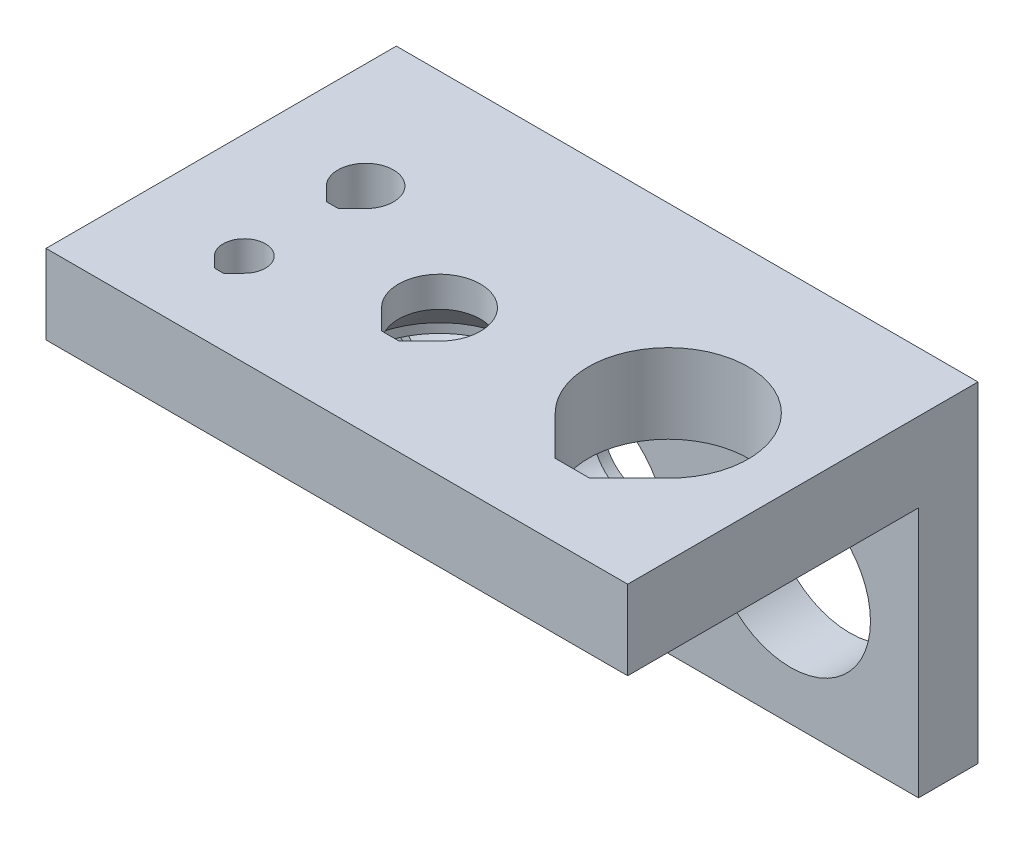
SolidWorks part; units mm, degrees
ref_plane "Front Plane" through (0, 0, 0) normal (0, 0, 1) x (1, 0, 0)
ref_plane "Top Plane" through (0, 0, 0) normal (0, 1, 0) x (1, 0, 0)
ref_plane "Right Plane" through (0, 0, 0) normal (1, 0, 0) x (0, 0, -1)
sketch "Sketch1" plane through (0, 0, 0) normal (0, 0, 1) x (1, 0, 0)
  line L1 (-22, -12.5) -> (22, -12.5)
  line L2 (-22, -12.5) -> (-22, 12.5)
  line L3 (-22, 12.5) -> (22, 12.5)
  line L4 (22, -12.5) -> (22, 12.5)
  line L5 (-22, -12.5) -> (22, 12.5) construction
  line L6 (-22, 12.5) -> (22, -12.5) construction
  point P0 (0, 0)
  dimension "D1" = 25
  dimension "D2" = 44
extrude "Boss-Extrude1" add sketch "Sketch1" along normal blind 4.5
sketch "Sketch2" plane through (0, 0, 4.5) normal (0, 0, 1) x (1, 0, 0)
  line L0 (22, -12.5) -> (22, 12.5) construction
  line L1 (-22, 12.5) -> (22, 12.5)
  line L2 (-22, 12.5) -> (-22, 6.5)
  line L3 (-22, 6.5) -> (22, 6.5)
  line L4 (22, 12.5) -> (22, 6.5)
  dimension "D1" = 6
extrude "Boss-Extrude2" add sketch "Sketch2" along normal blind 22
sketch "Sketch3" plane through (0, 0, 4.5) normal (0, 0, 1) x (1, 0, 0)
  line L0 (-22, -12.5) -> (22, -12.5) construction
  line L1 (-22, 6.5) -> (-22, -12.5) construction
  circle A0 centre (-14, -8.5) radius 1.6
  circle A1 centre (-14, 0.6825) radius 2.1
  circle A2 centre (-3.2346, -4.5) radius 3.1
  circle A3 centre (12.316, -2.7437) radius 6.05
  dimension "D1" = 3.2
  dimension "D2" = 4.2
  dimension "D3" = 6.2
  dimension "D4" = 12.1
  dimension "D5" = 4
  dimension "D6" = 8
  dimension "D7" = 8
extrude "Cut-Extrude1" cut sketch "Sketch3" against normal through all
sketch "Sketch4" plane through (0, 0, 4.5) normal (0, 0, 1) x (1, 0, 0)
  circle A0 centre (-3.2346, -4.5) radius 6.1
  dimension "D1" = 12.2
extrude "Cut-Extrude2" cut sketch "Sketch4" against normal blind 0.7
sketch "Sketch5" plane through (0, 0, 4.5) normal (0, 0, 1) x (1, 0, 0)
  circle A0 centre (-14, 0.6825) radius 4.1
  circle A1 centre (-14, 0.6825) radius 2.1 construction
  dimension "D1" = 8.2
extrude "Cut-Extrude3" cut sketch "Sketch5" against normal blind 0.5
sketch "Sketch6" plane through (0, 0, 4.5) normal (0, 0, 1) x (1, 0, 0)
  circle A0 centre (-14, -8.5) radius 3.1
  dimension "D1" = 6.2
extrude "Cut-Extrude4" cut sketch "Sketch6" against normal blind 0.4
chamfer "Chamfer4" distance 3 angle 45 1 edges at (-0.1346, -4.5, 3.8)
chamfer "Chamfer5" distance 2 angle 45 1 edges at (-11.9, 0.6825, 4)
chamfer "Chamfer6" distance 1.5 angle 45 1 edges at (-12.4, -8.5, 4.1)
ref_plane "Plane1" through (0, 5.5, 5.5) normal (0, -0.7071, -0.7071) x (1, 0, 0)
mirror "Mirror1" about plane through (0, 5.5, 5.5) normal (0, -0.7071, -0.7071) of "Chamfer6", "Chamfer5", "Chamfer4", "Cut-Extrude4", "Cut-Extrude3", "Cut-Extrude2", "Cut-Extrude1"
sketch "Sketch7" plane through (0, 12.5, 0) normal (0, 1, 0) x (1, 0, 0)
  line L0 (-14.3427, -21.42) -> (-13.6573, -21.42)
  line L1 (-13.6573, -21.42) -> (-12.8686, -20.6314)
  line L2 (-14.3427, -21.42) -> (-15.1314, -20.6314)
  line L3 (-14, -21.42) -> (-14, -19.5) construction
  line L4 (-15.1314, -20.6314) -> (-14, -19.5)
  line L5 (-14, -19.5) -> (-12.8686, -20.6314)
  line L6 (-3.2346, -15.5) -> (-1.0426, -17.692)
  line L7 (-1.0426, -17.692) -> (-2.5706, -19.22)
  line L8 (-3.8987, -19.22) -> (-5.4267, -17.692)
  line L9 (-5.4267, -17.692) -> (-3.2346, -15.5)
  line L10 (-3.8987, -19.22) -> (-2.5706, -19.22)
  line L11 (-3.2346, -15.5) -> (-3.2346, -19.22) construction
  line L12 (12.316, -13.7437) -> (16.594, -18.0216)
  line L13 (16.594, -18.0216) -> (13.622, -20.9937)
  line L14 (13.622, -20.9937) -> (11.01, -20.9937)
  line L15 (11.01, -20.9937) -> (8.038, -18.0216)
  line L16 (8.038, -18.0216) -> (12.316, -13.7437)
  line L17 (12.316, -20.9937) -> (12.316, -13.7437) construction
  line L18 (-14, -10.3175) -> (-12.5151, -11.8024)
  line L19 (-12.5151, -11.8024) -> (-13.5502, -12.8375)
  line L20 (-13.5502, -12.8375) -> (-14.4498, -12.8375)
  line L21 (-14.4498, -12.8375) -> (-15.4849, -11.8024)
  line L22 (-15.4849, -11.8024) -> (-14, -10.3175)
  line L23 (-14, -12.8375) -> (-14, -10.3175) construction
  circle A0 centre (-14, -19.5) radius 1.6 construction
  circle A1 centre (-3.2346, -15.5) radius 3.1 construction
  circle A2 centre (12.316, -13.7437) radius 6.05 construction
  circle A3 centre (-14, -10.3175) radius 2.1 construction
  point P8 (-14, -21.1)
  point P18 (8.6052, -4.1806)
  point P19 (-3.2346, -18.6)
  point P29 (12.316, -19.7937)
  point P39 (-14, -12.4175)
  dimension "D1" = 0.32
  dimension "D2" = 0.62
  dimension "D3" = 1.2
  dimension "D4" = 0.42
extrude "Cut-Extrude5" cut sketch "Sketch7" against normal through all
